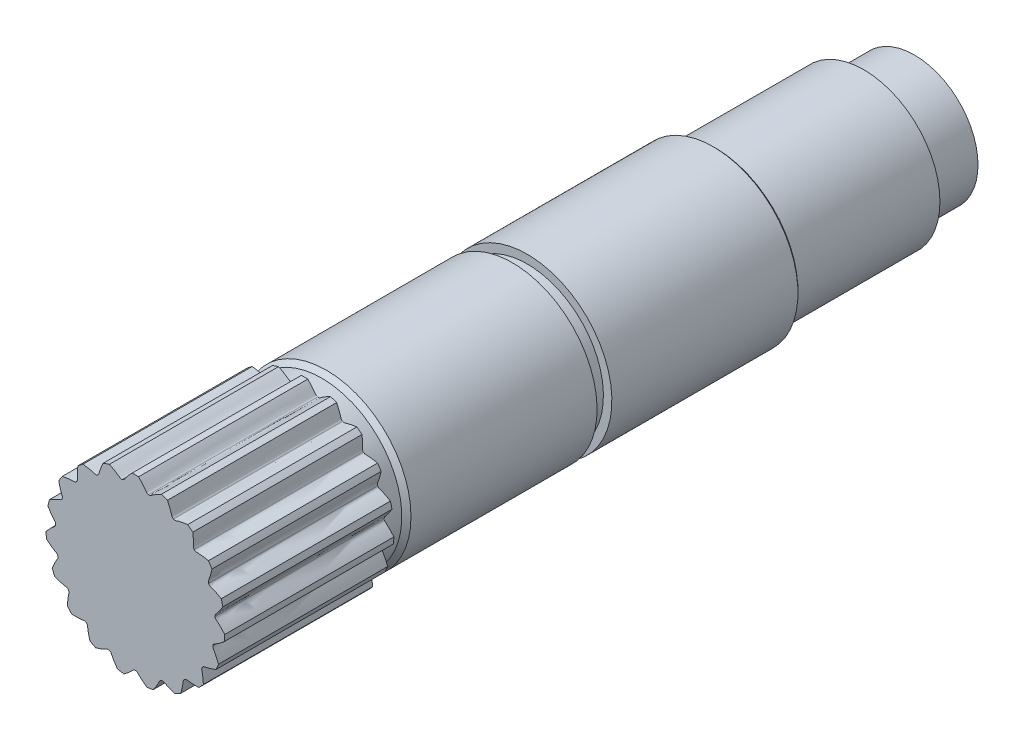
SolidWorks part; units mm, degrees
material "Alloy Steel"
ref_plane "Front Plane" through (0, 0, 0) normal (0, 0, 1) x (1, 0, 0)
ref_plane "Top Plane" through (0, 0, 0) normal (0, 1, 0) x (1, 0, 0)
ref_plane "Right Plane" through (0, 0, 0) normal (1, 0, 0) x (0, 0, -1)
sketch "Sketch12" plane through (0, 0, 0) normal (0, 0, 1) x (1, 0, 0)
  circle A0 centre (0, 0) radius 10
  dimension "D1" = 20
extrude "Shaft" add sketch "Sketch12" along normal mid plane 43
sketch "Sketch13" plane through (0, 0, 21.5) normal (0, 0, 1) x (1, 0, 0)
  circle A0 centre (0, 0) radius 9.4556
  dimension "D1" = 18.9113
extrude "Motor side relief" add sketch "Sketch13" along normal blind 1.587
sketch "Sketch14" plane through (0, 0, -21.5) normal (0, 0, -1) x (-1, 0, 0)
  circle A0 centre (0, 0) radius 8.3981
  dimension "D1" = 16.7963
sketch "Sketch15" plane through (0, 0, 23.087) normal (0, 0, 1) x (1, 0, 0)
  line L0 (5.7898, -7.4758) -> (5.8078, -7.4618)
  line L1 (5.8078, -7.4618) -> (5.8257, -7.4478)
  line L2 (7.9035, -5.1908) -> (7.9159, -5.1717)
  line L3 (7.9159, -5.1717) -> (7.9284, -5.1527)
  line L4 (9.1607, -2.3432) -> (9.1663, -2.3212)
  line L5 (9.1663, -2.3212) -> (9.1719, -2.2992)
  line L6 (9.4252, 0.7582) -> (9.4233, 0.7808)
  line L7 (9.4233, 0.7808) -> (9.4214, 0.8035)
  line L8 (8.6683, 3.7775) -> (8.6592, 3.7983)
  line L9 (8.6592, 3.7983) -> (8.6501, 3.8191)
  line L10 (6.9721, 6.3874) -> (6.9567, 6.4041)
  line L11 (6.9567, 6.4041) -> (6.9413, 6.4208)
  line L12 (4.5204, 8.3051) -> (4.5004, 8.316)
  line L13 (4.5004, 8.316) -> (4.4804, 8.3268)
  line L14 (1.5788, 9.3229) -> (1.5563, 9.3267)
  line L15 (1.5563, 9.3267) -> (1.5339, 9.3304)
  line L16 (-1.5339, 9.3304) -> (-1.5563, 9.3267)
  line L17 (-1.5563, 9.3267) -> (-1.5788, 9.3229)
  line L18 (-4.4804, 8.3268) -> (-4.5004, 8.316)
  line L19 (-4.5004, 8.316) -> (-4.5204, 8.3051)
  line L20 (-6.9413, 6.4208) -> (-6.9567, 6.4041)
  line L21 (-6.9567, 6.4041) -> (-6.9721, 6.3874)
  line L22 (-8.6501, 3.8191) -> (-8.6592, 3.7983)
  line L23 (-8.6592, 3.7983) -> (-8.6683, 3.7775)
  line L24 (-9.4214, 0.8035) -> (-9.4233, 0.7808)
  line L25 (-9.4233, 0.7808) -> (-9.4252, 0.7582)
  line L26 (-9.1719, -2.2992) -> (-9.1663, -2.3212)
  line L27 (-9.1663, -2.3212) -> (-9.1607, -2.3432)
  line L28 (-7.9284, -5.1527) -> (-7.9159, -5.1717)
  line L29 (-7.9159, -5.1717) -> (-7.9035, -5.1908)
  line L30 (-5.8257, -7.4478) -> (-5.8078, -7.4618)
  line L31 (-5.8078, -7.4618) -> (-5.7898, -7.4758)
  line L32 (-3.0917, -8.9359) -> (-3.0702, -8.9433)
  line L33 (-3.0702, -8.9433) -> (-3.0487, -8.9507)
  line L34 (-0.0227, -9.4556) -> (0, -9.4556)
  line L35 (0, -9.4556) -> (0.0227, -9.4556)
  line L36 (3.0487, -8.9507) -> (3.0702, -8.9433)
  line L37 (3.0702, -8.9433) -> (3.0917, -8.9359)
  arc A0 (4.6925, -9.4774) -> (5.3676, -9.1121) centre (0, 0) ccw
  arc A1 (7.5156, -7.4402) -> (8.0355, -6.8755) centre (0, 0) ccw
  arc A2 (9.5242, -4.5968) -> (9.8326, -3.8939) centre (0, 0) ccw
  arc A3 (10.5007, -1.2552) -> (10.5641, -0.4903) centre (0, 0) ccw
  arc A4 (10.3394, 2.2224) -> (10.1509, 2.9665) centre (0, 0) ccw
  arc A5 (9.0575, 5.4591) -> (8.6377, 6.1017) centre (0, 0) ccw
  arc A6 (6.7942, 8.1043) -> (6.1885, 8.5758) centre (0, 0) ccw
  arc A7 (3.7946, 9.8713) -> (3.0686, 10.1205) centre (0, 0) ccw
  arc A8 (0.3838, 10.5685) -> (-0.3838, 10.5685) centre (0, 0) ccw
  arc A9 (-3.0686, 10.1205) -> (-3.7946, 9.8713) centre (0, 0) ccw
  arc A10 (-6.1885, 8.5758) -> (-6.7942, 8.1043) centre (0, 0) ccw
  arc A11 (-8.6377, 6.1017) -> (-9.0575, 5.4591) centre (0, 0) ccw
  arc A12 (-10.1509, 2.9665) -> (-10.3394, 2.2224) centre (0, 0) ccw
  arc A13 (-10.5641, -0.4903) -> (-10.5007, -1.2552) centre (0, 0) ccw
  arc A14 (-9.8326, -3.8939) -> (-9.5242, -4.5968) centre (0, 0) ccw
  arc A15 (-8.0355, -6.8755) -> (-7.5156, -7.4402) centre (0, 0) ccw
  arc A16 (-5.3676, -9.1121) -> (-4.6925, -9.4774) centre (0, 0) ccw
  arc A17 (-2.1181, -10.3612) -> (-1.361, -10.4876) centre (0, 0) ccw
  arc A18 (1.361, -10.4876) -> (2.1181, -10.3612) centre (0, 0) ccw
  spline S0 degree 3 poles (3.0917, -8.9359) (3.1544, -8.9142) (3.2184, -8.911) (3.3396, -8.938) (3.397, -8.9729) (3.5767, -9.0624) (3.828, -9.1783) (4.24, -9.3384) (4.5379, -9.4334) (4.6925, -9.4774) knots 0 0 0 0 0.125 0.125 0.25 0.25 0.5 0.75 1 1 1 1
  spline S1 degree 3 poles (5.3676, -9.1121) (5.4153, -8.9586) (5.4987, -8.6572) (5.5901, -8.2247) (5.6305, -7.951) (5.6538, -7.7516) (5.656, -7.6845) (5.6997, -7.5682) (5.7374, -7.5164) (5.7898, -7.4758) knots 0 0 0 0 0.25 0.5 0.75 0.75 0.875 0.875 1 1 1 1
  spline S2 degree 3 poles (5.8257, -7.4478) (5.8779, -7.407) (5.9374, -7.3832) (6.0608, -7.3694) (6.1265, -7.3837) (6.3255, -7.41) (6.6008, -7.438) (7.0425, -7.4557) (7.3551, -7.4488) (7.5156, -7.4402) knots 0 0 0 0 0.125 0.125 0.25 0.25 0.5 0.75 1 1 1 1
  spline S3 degree 3 poles (8.0355, -6.8755) (8.0308, -6.7148) (8.0117, -6.4027) (7.9577, -5.964) (7.9071, -5.692) (7.8645, -5.4958) (7.8447, -5.4316) (7.8483, -5.3075) (7.8671, -5.2462) (7.9035, -5.1908) knots 0 0 0 0 0.25 0.5 0.75 0.75 0.875 0.875 1 1 1 1
  spline S4 degree 3 poles (7.9284, -5.1527) (7.9645, -5.0971) (8.013, -5.0552) (8.1253, -5.0021) (8.192, -4.9944) (8.3888, -4.9546) (8.6583, -4.8918) (9.0817, -4.765) (9.3752, -4.6571) (9.5242, -4.5968) knots 0 0 0 0 0.125 0.125 0.25 0.25 0.5 0.75 1 1 1 1
  spline S5 degree 3 poles (9.8326, -3.8939) (9.7759, -3.7434) (9.6566, -3.4544) (9.4631, -3.057) (9.3268, -2.8161) (9.2228, -2.6445) (9.1833, -2.5901) (9.1463, -2.4716) (9.1443, -2.4075) (9.1607, -2.3432) knots 0 0 0 0 0.25 0.5 0.75 0.75 0.875 0.875 1 1 1 1
  spline S6 degree 3 poles (9.1719, -2.2992) (9.188, -2.2349) (9.2203, -2.1795) (9.3092, -2.0928) (9.3699, -2.0638) (9.543, -1.9624) (9.7775, -1.8154) (10.1368, -1.558) (10.3793, -1.3606) (10.5007, -1.2552) knots 0 0 0 0 0.125 0.125 0.25 0.25 0.5 0.75 1 1 1 1
  spline S7 degree 3 poles (10.5641, -0.4903) (10.4617, -0.3663) (10.255, -0.1317) (9.9429, 0.1813) (9.7359, 0.3649) (9.5818, 0.4935) (9.5267, 0.532) (9.4533, 0.6322) (9.4305, 0.6921) (9.4252, 0.7582) knots 0 0 0 0 0.25 0.5 0.75 0.75 0.875 0.875 1 1 1 1
  spline S8 degree 3 poles (9.4214, 0.8035) (9.4158, 0.8695) (9.4284, 0.9324) (9.4844, 1.0433) (9.5323, 1.0904) (9.6631, 1.2426) (9.8372, 1.4577) (10.0935, 1.8179) (10.2588, 2.0833) (10.3394, 2.2224) knots 0 0 0 0 0.125 0.125 0.25 0.25 0.5 0.75 1 1 1 1
  spline S9 degree 3 poles (10.1509, 2.9665) (10.0138, 3.0504) (9.7422, 3.2052) (9.3453, 3.4) (9.0899, 3.5063) (8.9024, 3.5779) (8.8378, 3.5965) (8.7358, 3.6674) (8.6948, 3.7167) (8.6683, 3.7775) knots 0 0 0 0 0.25 0.5 0.75 0.75 0.875 0.875 1 1 1 1
  spline S10 degree 3 poles (8.6501, 3.8191) (8.6233, 3.8797) (8.6148, 3.9433) (8.6317, 4.0663) (8.6618, 4.1264) (8.7361, 4.3129) (8.8308, 4.5729) (8.9563, 4.9967) (9.0265, 5.3014) (9.0575, 5.4591) knots 0 0 0 0 0.125 0.125 0.25 0.25 0.5 0.75 1 1 1 1
  spline S11 degree 3 poles (8.6377, 6.1017) (8.4808, 6.1366) (8.1736, 6.1948) (7.735, 6.2502) (7.4588, 6.2678) (7.2583, 6.2747) (7.1911, 6.2713) (7.0717, 6.3052) (7.0169, 6.3385) (6.9721, 6.3874) knots 0 0 0 0 0.25 0.5 0.75 0.75 0.875 0.875 1 1 1 1
  spline S12 degree 3 poles (6.9413, 6.4208) (6.8963, 6.4695) (6.8676, 6.5268) (6.8437, 6.6487) (6.8526, 6.7153) (6.8624, 6.9158) (6.8676, 7.1925) (6.8486, 7.6341) (6.816, 7.9451) (6.7942, 8.1043) knots 0 0 0 0 0.125 0.125 0.25 0.25 0.5 0.75 1 1 1 1
  spline S13 degree 3 poles (6.1885, 8.5758) (6.0287, 8.5578) (5.7193, 8.5131) (5.2865, 8.4231) (5.0196, 8.3501) (4.8276, 8.2914) (4.7652, 8.2664) (4.6412, 8.2597) (4.5786, 8.2734) (4.5204, 8.3051) knots 0 0 0 0 0.25 0.5 0.75 0.75 0.875 0.875 1 1 1 1
  spline S14 degree 3 poles (4.4804, 8.3268) (4.422, 8.3582) (4.3763, 8.4031) (4.3141, 8.5106) (4.3009, 8.5765) (4.245, 8.7693) (4.1601, 9.0326) (3.9988, 9.4442) (3.8669, 9.7277) (3.7946, 9.8713) knots 0 0 0 0 0.125 0.125 0.25 0.25 0.5 0.75 1 1 1 1
  spline S15 degree 3 poles (3.0686, 10.1205) (2.9233, 10.0517) (2.6452, 9.9089) (2.2651, 9.6832) (2.0363, 9.5275) (1.8738, 9.4097) (1.8229, 9.3658) (1.7078, 9.3192) (1.6441, 9.3118) (1.5788, 9.3229) knots 0 0 0 0 0.25 0.5 0.75 0.75 0.875 0.875 1 1 1 1
  spline S16 degree 3 poles (1.5339, 9.3304) (1.4685, 9.3411) (1.4107, 9.3688) (1.3169, 9.4502) (1.283, 9.5083) (1.1676, 9.6725) (1.0018, 9.894) (0.7156, 10.2309) (0.4988, 10.4563) (0.3838, 10.5685) knots 0 0 0 0 0.125 0.125 0.25 0.25 0.5 0.75 1 1 1 1
  spline S17 degree 3 poles (-0.3838, 10.5685) (-0.4988, 10.4563) (-0.7156, 10.2309) (-1.0018, 9.894) (-1.1676, 9.6725) (-1.283, 9.5083) (-1.3169, 9.4502) (-1.4107, 9.3688) (-1.4685, 9.3411) (-1.5339, 9.3304) knots 0 0 0 0 0.25 0.5 0.75 0.75 0.875 0.875 1 1 1 1
  spline S18 degree 3 poles (-1.5788, 9.3229) (-1.6441, 9.3118) (-1.7078, 9.3192) (-1.8229, 9.3658) (-1.8738, 9.4097) (-2.0363, 9.5275) (-2.2651, 9.6832) (-2.6452, 9.9089) (-2.9233, 10.0517) (-3.0686, 10.1205) knots 0 0 0 0 0.125 0.125 0.25 0.25 0.5 0.75 1 1 1 1
  spline S19 degree 3 poles (-3.7946, 9.8713) (-3.8669, 9.7277) (-3.9988, 9.4442) (-4.1601, 9.0326) (-4.245, 8.7693) (-4.3009, 8.5765) (-4.3141, 8.5106) (-4.3763, 8.4031) (-4.422, 8.3582) (-4.4804, 8.3268) knots 0 0 0 0 0.25 0.5 0.75 0.75 0.875 0.875 1 1 1 1
  spline S20 degree 3 poles (-4.5204, 8.3051) (-4.5786, 8.2734) (-4.6412, 8.2597) (-4.7652, 8.2664) (-4.8276, 8.2914) (-5.0196, 8.3501) (-5.2865, 8.4231) (-5.7193, 8.5131) (-6.0287, 8.5578) (-6.1885, 8.5758) knots 0 0 0 0 0.125 0.125 0.25 0.25 0.5 0.75 1 1 1 1
  spline S21 degree 3 poles (-6.7942, 8.1043) (-6.816, 7.9451) (-6.8486, 7.6341) (-6.8676, 7.1925) (-6.8624, 6.9158) (-6.8526, 6.7153) (-6.8437, 6.6487) (-6.8676, 6.5268) (-6.8963, 6.4695) (-6.9413, 6.4208) knots 0 0 0 0 0.25 0.5 0.75 0.75 0.875 0.875 1 1 1 1
  spline S22 degree 3 poles (-6.9721, 6.3874) (-7.0169, 6.3385) (-7.0717, 6.3052) (-7.1911, 6.2713) (-7.2583, 6.2747) (-7.4588, 6.2678) (-7.735, 6.2502) (-8.1736, 6.1948) (-8.4808, 6.1366) (-8.6377, 6.1017) knots 0 0 0 0 0.125 0.125 0.25 0.25 0.5 0.75 1 1 1 1
  spline S23 degree 3 poles (-9.0575, 5.4591) (-9.0265, 5.3014) (-8.9563, 4.9967) (-8.8308, 4.5729) (-8.7361, 4.3129) (-8.6618, 4.1264) (-8.6317, 4.0663) (-8.6148, 3.9433) (-8.6233, 3.8797) (-8.6501, 3.8191) knots 0 0 0 0 0.25 0.5 0.75 0.75 0.875 0.875 1 1 1 1
  spline S24 degree 3 poles (-8.6683, 3.7775) (-8.6948, 3.7167) (-8.7358, 3.6674) (-8.8378, 3.5965) (-8.9024, 3.5779) (-9.0899, 3.5063) (-9.3453, 3.4) (-9.7422, 3.2052) (-10.0138, 3.0504) (-10.1509, 2.9665) knots 0 0 0 0 0.125 0.125 0.25 0.25 0.5 0.75 1 1 1 1
  spline S25 degree 3 poles (-10.3394, 2.2224) (-10.2588, 2.0833) (-10.0935, 1.8179) (-9.8372, 1.4577) (-9.6631, 1.2426) (-9.5323, 1.0904) (-9.4844, 1.0433) (-9.4284, 0.9324) (-9.4158, 0.8695) (-9.4214, 0.8035) knots 0 0 0 0 0.25 0.5 0.75 0.75 0.875 0.875 1 1 1 1
  spline S26 degree 3 poles (-9.4252, 0.7582) (-9.4305, 0.6921) (-9.4533, 0.6322) (-9.5267, 0.532) (-9.5818, 0.4935) (-9.7359, 0.3649) (-9.9429, 0.1813) (-10.255, -0.1317) (-10.4617, -0.3663) (-10.5641, -0.4903) knots 0 0 0 0 0.125 0.125 0.25 0.25 0.5 0.75 1 1 1 1
  spline S27 degree 3 poles (-10.5007, -1.2552) (-10.3793, -1.3606) (-10.1368, -1.558) (-9.7775, -1.8154) (-9.543, -1.9624) (-9.3699, -2.0638) (-9.3092, -2.0928) (-9.2203, -2.1795) (-9.188, -2.2349) (-9.1719, -2.2992) knots 0 0 0 0 0.25 0.5 0.75 0.75 0.875 0.875 1 1 1 1
  spline S28 degree 3 poles (-9.1607, -2.3432) (-9.1443, -2.4075) (-9.1463, -2.4716) (-9.1833, -2.5901) (-9.2228, -2.6445) (-9.3268, -2.8161) (-9.4631, -3.057) (-9.6566, -3.4544) (-9.7759, -3.7434) (-9.8326, -3.8939) knots 0 0 0 0 0.125 0.125 0.25 0.25 0.5 0.75 1 1 1 1
  spline S29 degree 3 poles (-9.5242, -4.5968) (-9.3752, -4.6571) (-9.0817, -4.765) (-8.6583, -4.8918) (-8.3888, -4.9546) (-8.192, -4.9944) (-8.1253, -5.0021) (-8.013, -5.0552) (-7.9645, -5.0971) (-7.9284, -5.1527) knots 0 0 0 0 0.25 0.5 0.75 0.75 0.875 0.875 1 1 1 1
  spline S30 degree 3 poles (-7.9035, -5.1908) (-7.8671, -5.2462) (-7.8483, -5.3075) (-7.8447, -5.4316) (-7.8645, -5.4958) (-7.9071, -5.692) (-7.9577, -5.964) (-8.0117, -6.4027) (-8.0308, -6.7148) (-8.0355, -6.8755) knots 0 0 0 0 0.125 0.125 0.25 0.25 0.5 0.75 1 1 1 1
  spline S31 degree 3 poles (-7.5156, -7.4402) (-7.3551, -7.4488) (-7.0425, -7.4557) (-6.6008, -7.438) (-6.3255, -7.41) (-6.1265, -7.3837) (-6.0608, -7.3694) (-5.9374, -7.3832) (-5.8779, -7.407) (-5.8257, -7.4478) knots 0 0 0 0 0.25 0.5 0.75 0.75 0.875 0.875 1 1 1 1
  spline S32 degree 3 poles (-5.7898, -7.4758) (-5.7374, -7.5164) (-5.6997, -7.5682) (-5.656, -7.6845) (-5.6538, -7.7516) (-5.6305, -7.951) (-5.5901, -8.2247) (-5.4987, -8.6572) (-5.4153, -8.9586) (-5.3676, -9.1121) knots 0 0 0 0 0.125 0.125 0.25 0.25 0.5 0.75 1 1 1 1
  spline S33 degree 3 poles (-4.6925, -9.4774) (-4.5379, -9.4334) (-4.24, -9.3384) (-3.828, -9.1783) (-3.5767, -9.0624) (-3.397, -8.9729) (-3.3396, -8.938) (-3.2184, -8.911) (-3.1544, -8.9142) (-3.0917, -8.9359) knots 0 0 0 0 0.25 0.5 0.75 0.75 0.875 0.875 1 1 1 1
  spline S34 degree 3 poles (-3.0487, -8.9507) (-2.986, -8.972) (-2.9335, -9.0088) (-2.8544, -9.1046) (-2.8306, -9.1674) (-2.7437, -9.3484) (-2.6166, -9.5942) (-2.3898, -9.9736) (-2.2131, -10.2315) (-2.1181, -10.3612) knots 0 0 0 0 0.125 0.125 0.25 0.25 0.5 0.75 1 1 1 1
  spline S35 degree 3 poles (-1.361, -10.4876) (-1.229, -10.3957) (-0.9781, -10.2091) (-0.6404, -9.9239) (-0.4404, -9.7327) (-0.2995, -9.5898) (-0.2565, -9.5381) (-0.1506, -9.4732) (-0.089, -9.4555) (-0.0227, -9.4556) knots 0 0 0 0 0.25 0.5 0.75 0.75 0.875 0.875 1 1 1 1
  spline S36 degree 3 poles (0.0227, -9.4556) (0.089, -9.4555) (0.1506, -9.4732) (0.2565, -9.5381) (0.2995, -9.5898) (0.4404, -9.7327) (0.6404, -9.9239) (0.9781, -10.2091) (1.229, -10.3957) (1.361, -10.4876) knots 0 0 0 0 0.125 0.125 0.25 0.25 0.5 0.75 1 1 1 1
  spline S37 degree 3 poles (2.1181, -10.3612) (2.2131, -10.2315) (2.3898, -9.9736) (2.6166, -9.5942) (2.7437, -9.3484) (2.8306, -9.1674) (2.8544, -9.1046) (2.9335, -9.0088) (2.986, -8.972) (3.0487, -8.9507) knots 0 0 0 0 0.25 0.5 0.75 0.75 0.875 0.875 1 1 1 1
extrude "Motor spline" add sketch "Sketch15" along normal blind 20
chamfer "Chamfer3" distance 1 angle 45 1 edges at (10, 0, 21.5)
sketch "Sketch23" plane through (0, 0, -31.5) normal (-0.9227, 0.3855, 0) x (-0.3855, -0.9227, 0)
  line L0 (10, 30) -> (9, 30)
  line L1 (9, 30) -> (9, 28.25)
  line L2 (9, 28.25) -> (10, 28.25)
  line L3 (10, 28.25) -> (10, 30)
  line L4 (10, 10) -> (10, 52) construction
  line L5 (-13.85, 30) -> (13.85, 30) construction
  line L7 (0, 185.3358) -> (0, -121.609) construction
  dimension "D1" = 1.75
  dimension "D2" = 1
revolve "snap ring" cut sketch "Sketch23" angle 360 about L7
sketch "Sketch24" plane through (0, 0, 0) normal (0, 1, 0) x (1, 0, 0)
  line L3 (10, 21.5) -> (10, 25.5)
  line L5 (7.5, 43.5) -> (7.5, 49.5)
  line L6 (7.5, 49.5) -> (0, 49.5)
  line L7 (0, 49.5) -> (0, 21.5)
  line L8 (10, 21.5) -> (-10, 21.5) construction
  line L9 (0, 21.5) -> (10, 21.5)
  line L10 (0, 0) -> (0, 49.7252) construction
  line L12 (7.5, 43.5) -> (9, 43.5)
  line L14 (10, 25.5) -> (9, 25.5)
  line L15 (9, 25.5) -> (9, 43.5)
  dimension "D1" = 15
  dimension "D2" = 22
  dimension "D3" = 4
  dimension "D8" = 6
revolve "Revolve1" add sketch "Sketch24" angle 360 about L10
chamfer "Chamfer4" distance 1 angle 25 2 edges at (9, 0, -43.5) (7.5, 0, -49.5) first distance on face at (7.5, 0, -43.5) first distance on face at (7.5, 0, -49.5)
chamfer "Chamfer5" distance 0.25 angle 45 1 edges at (10, 0, -25.5)
